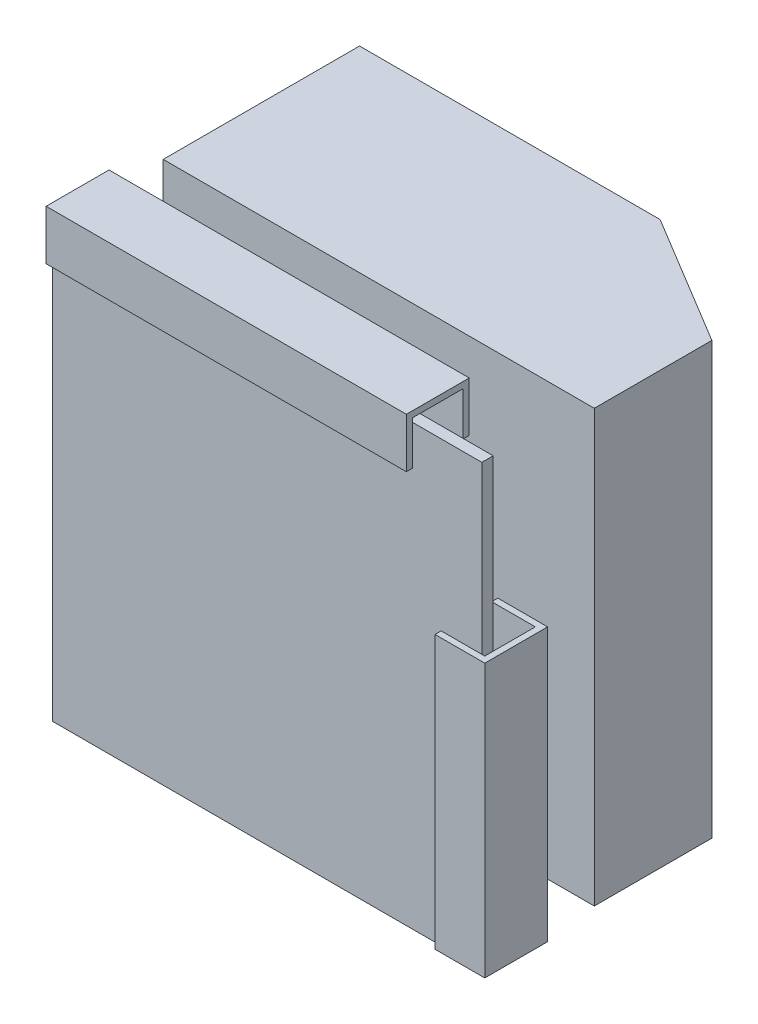
SolidWorks part; units mm, degrees
ref_plane "Front Plane" through (0, 0, 0) normal (0, 0, 1) x (1, 0, 0)
ref_plane "Top Plane" through (0, 0, 0) normal (0, 1, 0) x (1, 0, 0)
ref_plane "Right Plane" through (0, 0, 0) normal (1, 0, 0) x (0, 0, -1)
ref_plane "PY -55.000" through (0, -55, 0) normal (0, 1, 0) x (1, 0, 0)
sketch "housing sketch" plane through (0, -55, 0) normal (0, 1, 0) x (1, 0, 0)
  line L0 (0, 0) -> (0, 30)
  line L1 (0, 30) -> (-33.3047, 50.1)
  line L2 (-33.3047, 50.1) -> (-110, 50.1)
  line L3 (-110, 50.1) -> (-110, 0)
  line L4 (-110, 0) -> (0, 0)
extrude "housing" add sketch "housing sketch" along normal mid plane 110
ref_plane "PZ 26.850" through (0, 0, 26.85) normal (0, 0, 1) x (1, 0, 0)
sketch "diffuser sketch" plane through (0, 0, 26.85) normal (0, 0, 1) x (1, 0, 0)
  line L0 (-110, -110) -> (-0.4, -110)
  line L1 (-0.4, -110) -> (-0.4, 2)
  line L2 (-0.4, 2) -> (-110, 2)
  line L3 (-110, 2) -> (-110, -110)
extrude "diffuser" add sketch "diffuser sketch" along normal mid plane 2.9
ref_plane "PY -75.215" through (0, -75.215, 0) normal (0, 1, 0) x (1, 0, 0)
sketch "side channel sketch" plane through (0, -75.215, 0) normal (0, 1, 0) x (1, 0, 0)
  line L0 (-10.78, -13.83) -> (1.92, -13.83)
  line L1 (1.92, -13.83) -> (1.92, -29.87)
  line L2 (1.92, -29.87) -> (-10.78, -29.87)
  line L3 (-10.78, -29.87) -> (-10.78, -28.3)
  line L4 (-10.78, -28.3) -> (0.35, -28.3)
  line L5 (0.35, -28.3) -> (0.35, -15.4)
  line L6 (0.35, -15.4) -> (-10.78, -15.4)
  line L7 (-10.78, -15.4) -> (-10.78, -13.83)
extrude "side channel" add sketch "side channel sketch" along normal mid plane 69.57
ref_plane "PX -64.040" through (-64.04, 0, 0) normal (1, 0, 0) x (0, 0, -1)
sketch "end channel sketch" plane through (-64.04, 0, 0) normal (1, 0, 0) x (0, 0, -1)
  line L0 (-13.83, -8.13) -> (-13.83, 4.57)
  line L1 (-13.83, 4.57) -> (-29.87, 4.57)
  line L2 (-29.87, 4.57) -> (-29.87, -8.13)
  line L3 (-29.87, -8.13) -> (-28.3, -8.13)
  line L4 (-28.3, -8.13) -> (-28.3, 3)
  line L5 (-28.3, 3) -> (-15.4, 3)
  line L6 (-15.4, 3) -> (-15.4, -8.13)
  line L7 (-15.4, -8.13) -> (-13.83, -8.13)
extrude "end channel" add sketch "end channel sketch" along normal mid plane 91.92
equation "\"diffL\" = 608.8mm"
equation "\"diffW\" = 329.4mm"
equation "\"diffT\" = 2.9mm"
equation "\"chanSlotW\" = 12.9mm"
equation "\"chanSlotDepth\" = 11.13mm"
equation "\"chanFloor\" = 1.57mm"
equation "\"chanLeg\" = 12.7mm"
equation "\"lightL\" = 605mm"
equation "\"lightW\" = 331mm"
equation "\"lightH\" = 92mm"
equation "\"lightSideFlat\" = 30mm"
equation "\"lightSlopeLen\" = 33.1mm"
equation "\"lightWingDepth\" = 47.9mm"
equation "\"lightWingFlat\" = 90.2mm"
equation "\"lightChanW\" = 99.6mm"
equation "\"lightChanStand\" = 44.1mm"
equation "\"insFlangeD\" = 12.3mm"
equation "\"insFromEnd\" = 20.7mm"
equation "\"insUpSlope\" = 20.8mm"
equation "\"gaugeH\" = 10mm"
equation "\"gaugeStepLen\" = 14mm"
equation "\"gaugeStepW0\" = 13.1mm"
equation "\"gaugeStepDW\" = 0.2mm"
equation "\"gaugeSteps\" = 5mm"
equation "\"gaugeHandleLen\" = 30mm"
equation "\"gaugeHandleW\" = 24mm"
equation "\"gaugeSlot0\" = 3mm"
equation "\"gaugeSlotD\" = 0.1mm"
equation "\"gaugeSlotDepth\" = 8mm"
equation "\"gap\" = 25.4mm"
equation "\"edgeL\" = 1mm"
equation "\"edgeW\" = 0.75mm"
equation "\"proud\" = 1.5mm"
equation "\"seatClr\" = 0.15mm"
equation "\"tongueClrZ\" = 0.1mm"
equation "\"tongueClrX\" = 0.25mm"
equation "\"tongueLen\" = 30mm"
equation "\"armSide\" = 45mm"
equation "\"armEnd\" = 20mm"
equation "\"cornerCham\" = 3mm"
equation "\"brkW\" = 26mm"
equation "\"brkT\" = 7mm"
equation "\"brkSeatClr\" = 0.2mm"
equation "\"brkScrewSpan\" = 16mm"
equation "\"pilotD\" = 2.7mm"
equation "\"pilotDepth\" = 10mm"
equation "\"screwClrD\" = 3.9mm"
equation "\"jogBelow\" = 4mm"
equation "\"padT\" = 7mm"
equation "\"padLen\" = 31mm"
equation "\"m6Clr\" = 7mm"
equation "\"m6Slot\" = 3mm"
equation "\"flangeRelD\" = 17mm"
equation "\"flangeRelDepth\" = 1.5mm"
equation "\"relLen\" = 7mm"
equation "\"relDepth\" = 4mm"
equation "\"relLand\" = 2mm"
equation "\"knockN\" = 100mm"
equation "\"petgcfE\" = 3000mm"
equation "\"mockExtent\" = 110mm"
equation "\"relZnear\" = 9.4mm"
equation "\"relZfar\" = 23.4mm"
equation "\"headD\" = 8mm"
equation "\"headH\" = 2.5mm"
equation "\"headFromEnd\" = 6.8mm"
equation "\"headBack\" = 16.4mm"
equation "\"sideClr\" = 0.4mm"
